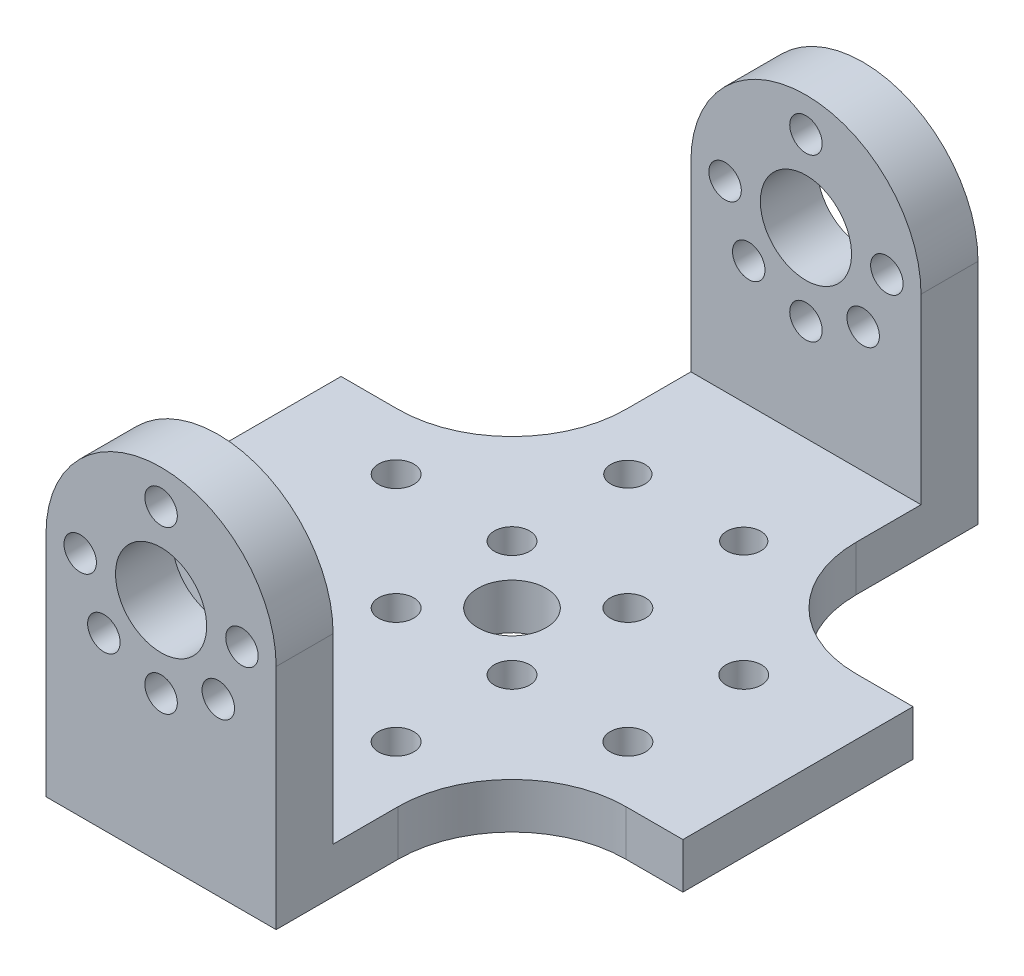
SolidWorks part; units mm, degrees
ref_plane "Front Plane" through (0, 0, 0) normal (0, 0, 1) x (1, 0, 0)
ref_plane "Top Plane" through (0, 0, 0) normal (0, 1, 0) x (1, 0, 0)
ref_plane "Right Plane" through (0, 0, 0) normal (1, 0, 0) x (0, 0, -1)
sketch "Sketch1" plane through (0, 0, 0) normal (0, 0, 1) x (1, 0, 0)
  line L0 (0, 4) -> (0, 5.6) construction
  line L5 (0, 5.6) -> (0, 7.1) construction
  line L6 (0, 8.525) -> (0, 10.1) construction
  line L7 (-10.1, 0) -> (-10.1, -20)
  line L8 (10.1, 0) -> (10.1, -20)
  line L9 (0, 0) -> (0, -18) construction
  line L10 (0, 0) -> (-10.1, 0) construction
  line L11 (0, 0) -> (10.1, 0) construction
  line L12 (-10.1, -20) -> (10.1, -20)
  arc A1 (10.1, 0) -> (-10.1, 0) centre (0, 0) ccw
  circle A2 centre (0, 0) radius 4
  circle A3 centre (0, 7.1) radius 1.425
  circle A5 centre (7.1, 0) radius 1.425
  circle A6 centre (5.0205, -5.0205) radius 1.425
  circle A7 centre (0, -7.1) radius 1.425
  circle A8 centre (-5.0205, -5.0205) radius 1.425
  circle A9 centre (-7.1, 0) radius 1.425
  circle A11 centre (-5.0205, 5.0205) radius 1.425 [skipped]
  circle A12 centre (5.0205, 5.0205) radius 1.425 [skipped]
  point P28 (0, 0)
  dimension "D3" = 1.6
  dimension "D1" = 20.2
  dimension "D2" = 8
  dimension "D5" = 2.85
  dimension "D6" = 1.575
  dimension "D4" = 1.5
  dimension "D9" = 20
  dimension "D10" = 20
  dimension "D7" = 8
extrude "Boss-Extrude1" add sketch "Sketch1" along normal blind 61.6
sketch "Sketch2" plane through (10.1, 0, 0) normal (1, 0, 0) x (0, 0, -1)
  line L0 (-30.8, 10.1) -> (-30.8, -20) construction
  line L1 (0, 10.1) -> (-61.6, 10.1) construction
  line L2 (-61.6, -20) -> (0, -20) construction
  line L3 (-5, 10.1) -> (-5, -20) construction
  line L4 (-11.7999, -18) -> (-56.6, -18)
  line L5 (0, 10.1) -> (0, -20) construction
  line L6 (-56.6, 10.1) -> (-56.6, -20) construction
  line L7 (-11.7999, -20) -> (-11.7999, -18) construction
  line L8 (-56.6, -18) -> (-56.6, 10.1)
  line L9 (-56.6, 10.1) -> (-5, 10.1)
  line L10 (-5, 10.1) -> (-5, -18)
  line L11 (-5, -18) -> (-11.7999, -18)
  dimension "D1" = 5
  dimension "D2" = 2
extrude "Cut-Extrude1" cut sketch "Sketch2" against normal blind 55.6
sketch "Sketch3" plane through (0, -20, 0) normal (0, -1, 0) x (1, 0, 0)
  line L0 (0, 61.6) -> (0, 0) construction
  line L1 (-10.1, 61.6) -> (10.1, 61.6) construction
  line L2 (0, 30.8) -> (-2.1213, 32.9213) construction
  line L3 (-3.9881, 34.7881) -> (-5.0841, 35.8841) construction
  line L4 (-5.0841, 37.4341) -> (-5.0841, 44.5041) construction
  line L5 (-5.0841, 44.5041) -> (-5.0841, 46.0541) construction
  line L6 (-10.1, 30.8) -> (10.1, 30.8) construction
  line L7 (-10.1, 61.6) -> (-10.1, 0) construction
  line L8 (10.1, 61.6) -> (10.1, 0) construction
  line L9 (-5.0841, 25.7159) -> (-5.0841, 15.5459) construction
  line L13 (-2.1213, 32.9213) -> (-3.9881, 34.7881) construction
  circle A0 centre (0, 30.8) radius 3
  circle A10 centre (-5.0841, 35.8841) radius 1.55
  circle A11 centre (5.0841, 35.8841) radius 1.55
  circle A12 centre (5.0841, 25.7159) radius 1.55
  circle A13 centre (-5.0841, 25.7159) radius 1.55
  circle A14 centre (-5.0841, 46.0541) radius 1.55
  circle A15 centre (5.0841, 46.0541) radius 1.55
  circle A16 centre (-5.0841, 15.5459) radius 1.5
  circle A17 centre (5.0841, 15.5459) radius 1.5
  point P38 (0, 30.8)
  dimension "D1" = 6
  dimension "D5" = 4
  dimension "D2" = 10.17
  dimension "D7" = 3.1
  dimension "D13" = 45
  dimension "D3" = 1.55
  dimension "D4" = 45
  dimension "D12" = 10.1682
  dimension "D14" = 5.0841
  dimension "D8" = 3
  dimension "D6" = 1.55
  dimension "D9" = 10.17
  dimension "D11" = 2.64
extrude "Cut-Extrude2" cut sketch "Sketch3" against normal blind 10 contours A11 | A12 | A17 | A14 | A10 | A0 | A13 | A15 | A16 region at (0, -20, 30.8) region at (-5.0841, -20, 35.8841) region at (5.0841, -20, 35.8841) region at (5.0841, -20, 25.7159) region at (-5.0841, -20, 25.7159) region at (-5.0841, -20, 46.0541) region at (5.0841, -20, 15.5459)
sketch "Sketch4" plane through (0, -18, 0) normal (0, 1, 0) x (1, 0, 0)
  line L1 (-10.1, -5) -> (10.1, -5)
  line L2 (-10.1, -5) -> (-10.1, -56.6)
  line L3 (-10.1, -56.6) -> (10.1, -56.6)
  line L4 (10.1, -5) -> (10.1, -56.6)
  line L5 (-10.1, -5) -> (10.1, -56.6) construction
  line L6 (-10.1, -56.6) -> (10.1, -5) construction
  circle A0 centre (0, -30.8) radius 3
  circle A1 centre (-5.0841, -25.7159) radius 1.55
  circle A2 centre (5.0841, -25.7159) radius 1.55
  circle A3 centre (5.0841, -15.5459) radius 1.5
  circle A4 centre (-5.0841, -15.5459) radius 1.5
  circle A5 centre (-5.0841, -35.8841) radius 1.55
  circle A6 centre (5.0841, -35.8841) radius 1.55
  circle A7 centre (-5.0841, -46.0541) radius 1.55
  circle A8 centre (5.0841, -46.0541) radius 1.55
extrude "Boss-Extrude2" add sketch "Sketch4" along normal blind 2
ref_plane "Plane1" through (0, -20, 0) normal (0, -1, 0) x (-1, 0, 0)
sketch "Sketch5" plane through (0, -20, 0) normal (0, -1, 0) x (-1, 0, 0)
  line L0 (10.1, 0) -> (10.1, -20.7) construction
  line L1 (10.1, -61.6) -> (10.1, 0) construction
  line L2 (10.1, -61.6) -> (10.1, -40.9) construction
  line L3 (10.1, -20.7) -> (10.1, -40.9)
  line L4 (10.1, -40.9) -> (25.1, -40.9)
  line L5 (10.1, -20.7) -> (25.1, -20.7)
  line L6 (25.1, -20.7) -> (25.1, -40.9)
  line L7 (0, 0) -> (0, -61.6) construction
  line L8 (10.1, -61.6) -> (-10.1, -61.6) construction
  line L9 (-10.1, -20.7) -> (-25.1, -20.7)
  line L10 (-10.1, -20.7) -> (-10.1, -40.9)
  line L11 (-10.1, -40.9) -> (-25.1, -40.9)
  line L12 (-25.1, -20.7) -> (-25.1, -40.9)
  dimension "D1" = 20.7
  dimension "D2" = 20.7
  dimension "D3" = 15
extrude "Boss-Extrude3" add sketch "Sketch5" against normal blind 4
ref_plane "Plane2" through (0, -20, 0) normal (0, -1, 0) x (-1, 0, 0)
ref_plane "Plane3" through (0, -20, 0) normal (0, -1, 0) x (-1, 0, 0)
sketch "Sketch6" plane through (0, -20, 0) normal (0, -1, 0) x (-1, 0, 0)
  line L0 (5.0841, -25.7159) -> (15.2541, -25.7159) construction
  line L2 (0, -20.0444) -> (0, -61.6) construction
  line L3 (10.1, -61.6) -> (-10.1, -61.6) construction
  line L4 (0, -30.8) -> (25.1, -30.8) construction
  line L5 (25.1, -40.9) -> (25.1, -20.7) construction
  circle A0 centre (15.2541, -25.7159) radius 1.55
  circle A1 centre (15.2541, -35.8841) radius 1.55
  circle A2 centre (-15.2541, -25.7159) radius 1.55
  circle A3 centre (-15.2541, -35.8841) radius 1.55
  dimension "D2" = 3.1
  dimension "D1" = 10.17
extrude "Cut-Extrude3" cut sketch "Sketch6" against normal blind 4
ref_plane "Plane4" through (10.1, 0, 0) normal (1, 0, 0) x (0, 0, -1)
fillet "Fillet1" radius 10 4 edges at (-10.1, -18, 20.7) (-10.1, -18, 40.9) (10.1, -18, 40.9) (10.1, -18, 20.7)
